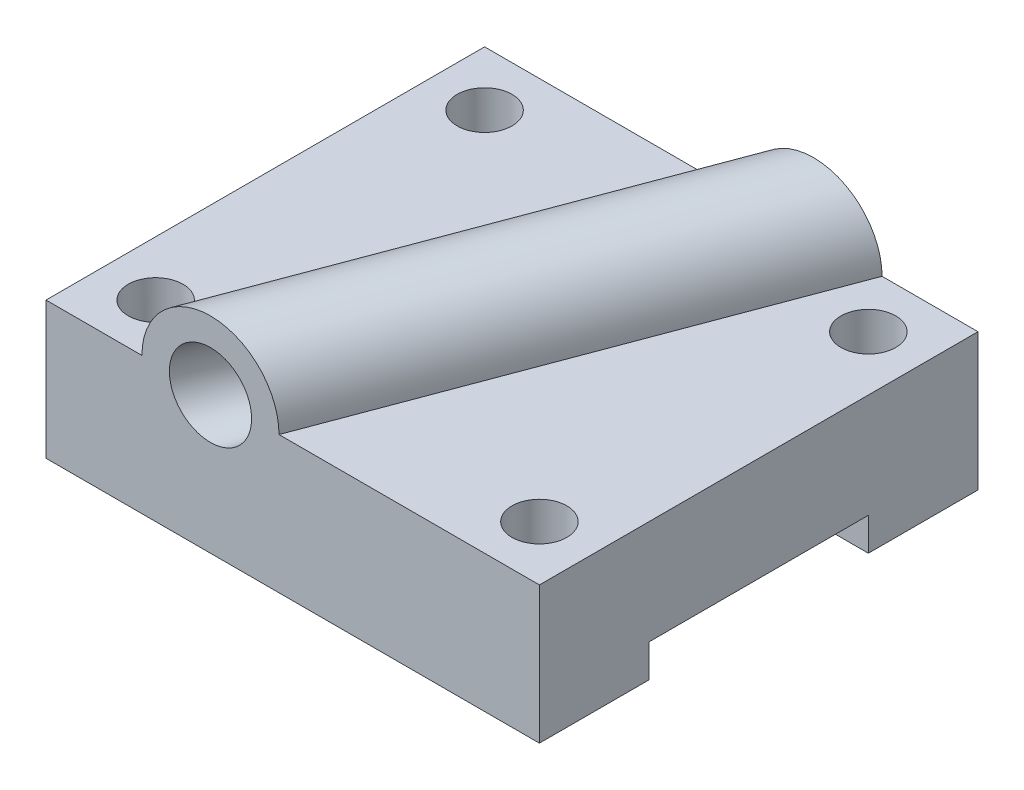
SolidWorks part; units mm, degrees
ref_plane "Alzado" through (0, 0, 0) normal (0, 0, 1) x (1, 0, 0)
ref_plane "Planta" through (0, 0, 0) normal (0, 1, 0) x (1, 0, 0)
ref_plane "Vista lateral" through (0, 0, 0) normal (1, 0, 0) x (0, 0, -1)
sketch "Croquis1" plane through (0, 0, 0) normal (1, 0, 0) x (0, 0, -1)
  line L0 (-40, 0) -> (-20, 0)
  line L1 (-40, 0) -> (-40, 25)
  line L2 (-40, 25) -> (40, 25)
  line L3 (40, 25) -> (40, 0)
  line L4 (-20, 0) -> (-20, 6)
  line L5 (-20, 6) -> (20, 6)
  line L6 (20, 6) -> (20, 0)
  line L7 (20, 0) -> (40, 0)
  point P4 (0, 0)
  dimension "D1" = 80
  dimension "D2" = 25
  dimension "D3" = 20
  dimension "D4" = 20
  dimension "D5" = 6
  dimension "D6" = 40
  dimension "D7" = 6
extrude "Saliente-Extruir1" add sketch "Croquis1" along normal blind 90
sketch "Croquis2" plane through (0, 25, 0) normal (0, 1, 0) x (1, 0, 0)
  line L0 (45, 40) -> (45, -40) construction
  line L1 (90, 40) -> (0, 40) construction
  line L2 (90, -40) -> (0, -40) construction
  line L3 (0, 0) -> (90, 0) construction
  line L4 (90, 40) -> (90, -40) construction
  line L5 (90, -40) -> (80, -40) construction
  line L6 (80, -40) -> (80, -30) construction
  circle A0 centre (80, -30) radius 5
  circle A1 centre (10, -30) radius 5
  circle A2 centre (80, 30) radius 5
  circle A3 centre (10, 30) radius 5
  dimension "D1" = 10
extrude "Cortar-Extruir1" cut sketch "Croquis2" against normal up to next
ref_plane "Plano1" through (0, 0, -40) normal (0, 0, -1) x (-1, 0, 0)
sketch "Croquis3" plane through (0, 0, -40) normal (0, 0, -1) x (-1, 0, 0)
  line L0 (-90, 25) -> (-60, 25) construction
  line L1 (-90, 25) -> (0, 25) construction
  line L2 (-72.5, 25) -> (-47.5, 25)
  arc A0 (-47.5, 25) -> (-72.5, 25) centre (-60, 25) ccw
  dimension "D2" = 25
  dimension "D1" = 30
sketch "Croquis4" plane through (0, 0, 40) normal (0, 0, 1) x (1, 0, 0)
  line L0 (0, 25) -> (30, 25) construction
  line L1 (90, 25) -> (0, 25) construction
  line L2 (17.5, 25) -> (42.5, 25)
  arc A0 (42.5, 25) -> (17.5, 25) centre (30, 25) ccw
  dimension "D1" = 25
  dimension "D2" = 30
loft "Recubrir4" add profiles "Croquis4", "Croquis3" connector at (42.5, 25, 40) connector at (72.5, 25, -40)
sketch "Croquis7" plane through (0, 0, 40) normal (0, 0, 1) x (1, 0, 0)
  circle A0 centre (30, 25) radius 7.5
  dimension "D1" = 15
sketch "Croquis8" plane through (0, 0, -40) normal (0, 0, -1) x (-1, 0, 0)
  circle A0 centre (-60, 25) radius 7.5
  dimension "D1" = 15
loft "Cortar-Recubrir1" cut profiles "Croquis8", "Croquis7" connector at (66.4747, 28.7853, -40) connector at (29.9717, 32.4999, 40)
